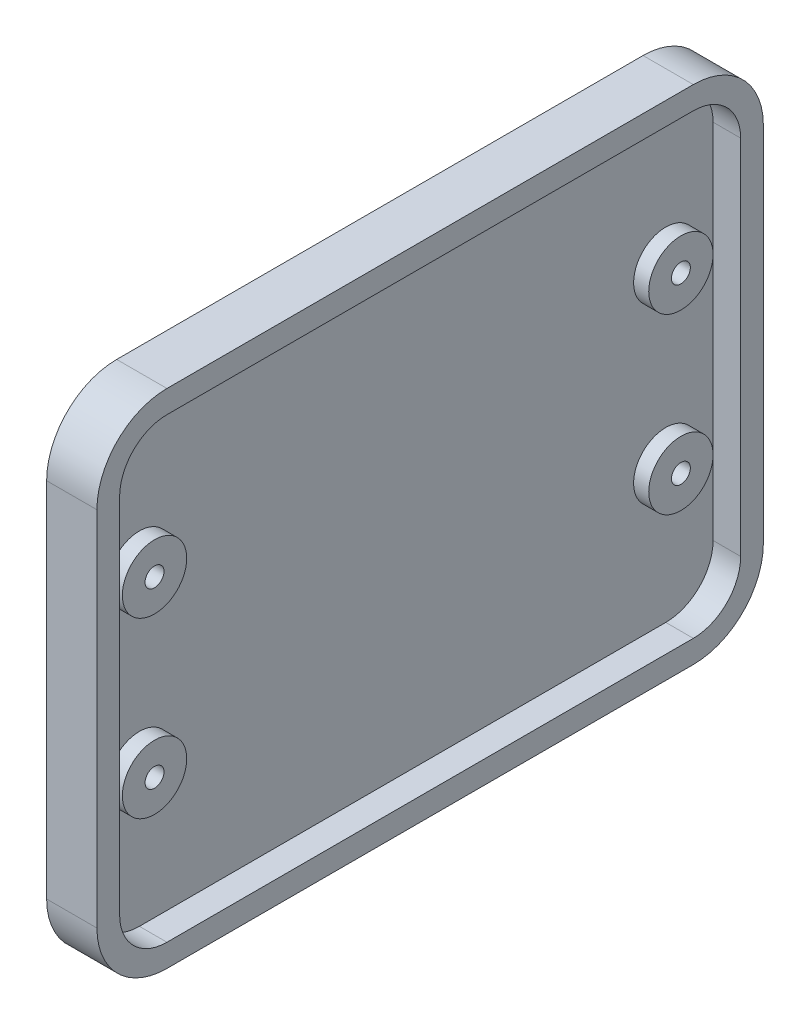
SolidWorks part; units mm, degrees
ref_plane "Front Plane" through (0, 0, 0) normal (0, 0, 1) x (1, 0, 0)
ref_plane "Top Plane" through (0, 0, 0) normal (0, 1, 0) x (1, 0, 0)
ref_plane "Right Plane" through (0, 0, 0) normal (1, 0, 0) x (0, 0, -1)
sketch "Sketch1" plane through (0, 0, 0) normal (1, 0, 0) x (0, 0, -1)
  line L0 (-6, 0.25) -> (-75.53, 0.25)
  line L1 (-6, 0) -> (-75.53, 0)
  line L2 (0, -6) -> (0, -53.85)
  line L3 (-6, -59.85) -> (-75.53, -59.85)
  line L4 (-81.53, -6) -> (-81.53, -53.85)
  line L5 (-81.78, -6) -> (-81.78, -53.85)
  line L6 (-6, -60.1) -> (-75.53, -60.1)
  line L7 (0.25, -6) -> (0.25, -53.85)
  line L8 (-6, 3.25) -> (-75.53, 3.25)
  line L9 (-84.78, -6) -> (-84.78, -53.85)
  line L10 (-6, -63.1) -> (-75.53, -63.1)
  line L11 (3.25, -6) -> (3.25, -53.85)
  circle A0 centre (-6, -19.12) radius 1.25
  circle A1 centre (-6, -42.05) radius 1.25
  circle A2 centre (-75.53, -19.12) radius 1.25
  circle A3 centre (-75.53, -42.05) radius 1.25
  arc A4 (-75.53, -59.85) -> (-81.53, -53.85) centre (-75.53, -53.85) cw
  arc A5 (0, -53.85) -> (-6, -59.85) centre (-6, -53.85) cw
  arc A6 (-6, 0) -> (0, -6) centre (-6, -6) cw
  arc A7 (-75.53, 0) -> (-81.53, -6) centre (-75.53, -6) ccw
  arc A8 (-75.53, 0.25) -> (-81.78, -6) centre (-75.53, -6) ccw
  arc A9 (-75.53, -60.1) -> (-81.78, -53.85) centre (-75.53, -53.85) cw
  arc A10 (0.25, -53.85) -> (-6, -60.1) centre (-6, -53.85) cw
  arc A11 (-6, 0.25) -> (0.25, -6) centre (-6, -6) cw
  arc A12 (-75.53, 3.25) -> (-84.78, -6) centre (-75.53, -6) ccw
  arc A13 (-75.53, -63.1) -> (-84.78, -53.85) centre (-75.53, -53.85) cw
  arc A14 (3.25, -53.85) -> (-6, -63.1) centre (-6, -53.85) cw
  arc A15 (-6, 3.25) -> (3.25, -6) centre (-6, -6) cw
  circle A16 centre (-75.53, -19.12) radius 4.25
  circle A17 centre (-6, -19.12) radius 4.25
  circle A18 centre (-6, -42.05) radius 4.25
  circle A19 centre (-75.53, -42.05) radius 4.25
  point P13 (0, 0)
  point P14 (0, 0)
  point P15 (0, 0)
  point P16 (0, 0)
  point P21 (0, -59.85)
  point P24 (0, 0)
  point P27 (-81.53, 0)
  dimension "D3" = 2.5
  dimension "D4" = 2.5
  dimension "D5" = 2.5
  dimension "D6" = 2.5
  dimension "D11" = 6
  dimension "D1" = 59.85
  dimension "D2" = 81.53
  dimension "D7" = 6
  dimension "D8" = 6
  dimension "D9" = 17.8
  dimension "D10" = 19.12
  dimension "D12" = 0.25
  dimension "D13" = 3
  dimension "D14" = 3
extrude "Boss-Extrude1" add sketch "Sketch1" against normal blind 3 contours L8 A12 L9 A13 L10 A14 L11 A15
extrude "Boss-Extrude2" add sketch "Sketch1<3>" along normal blind 2 contours A16 A2 | A17 A0 | A18 A1 | A19 A3 region at (0, -19.12, 79.6598) region at (0, -19.12, 10.1298) region at (0, -42.05, 10.1298) region at (0, -42.05, 79.6598)
sketch "Sketch1<3>" plane through (0, 0, 0) normal (1, 0, 0) x (0, 0, -1) same geometry as "Sketch1"
extrude "Boss-Extrude3" add sketch "Sketch1<4>" along normal blind 3.64 contours A15 L8 A12 L9 A13 L10 A14 L11 L0 A11 L7 A10 L6 A9 L5 A8 region at (0, -0.2387, 0.2387)
sketch "Sketch1<4>" plane through (0, 0, 0) normal (1, 0, 0) x (0, 0, -1) same geometry as "Sketch1"
extrude "Cut-Extrude1" cut sketch "Sketch1<5>" against normal up to next contours A2 | A0 | A1 | A3
sketch "Sketch1<5>" plane through (0, 0, 0) normal (1, 0, 0) x (0, 0, -1) same geometry as "Sketch1"
